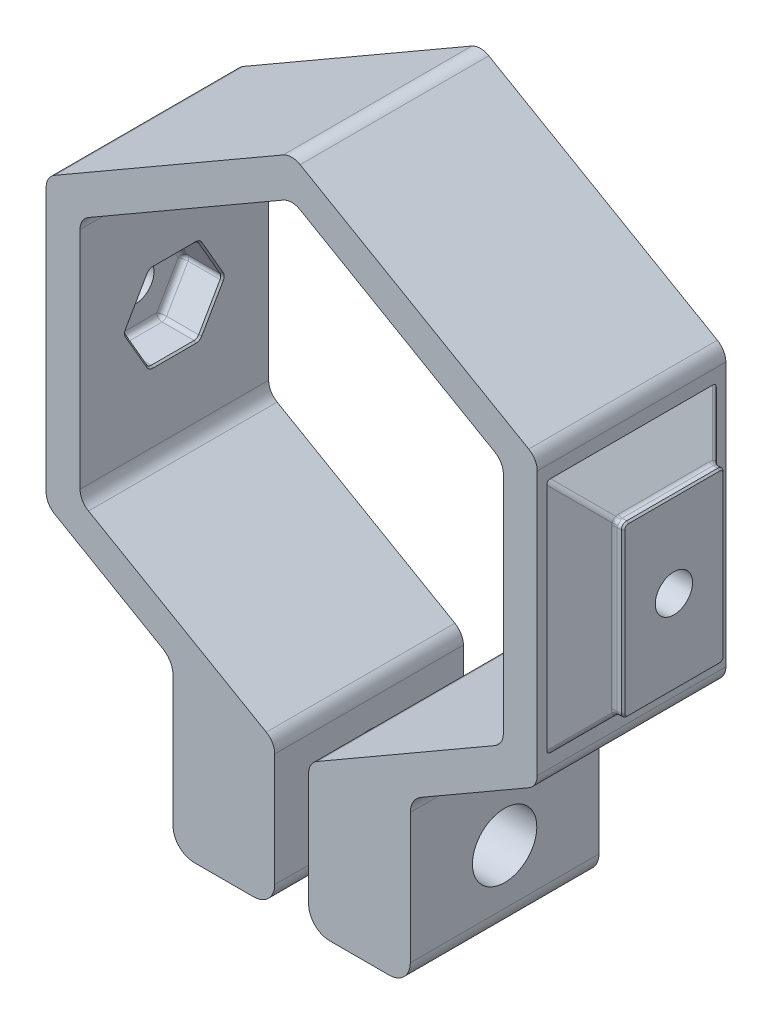
SolidWorks part; units mm, degrees
ref_plane "Front" through (0, 0, 0) normal (0, 0, 1) x (1, 0, 0)
ref_plane "Top" through (0, 0, 0) normal (0, 1, 0) x (1, 0, 0)
ref_plane "Right" through (0, 0, 0) normal (1, 0, 0) x (0, 0, -1)
sketch "Sketch1" plane through (0, 0, 0) normal (0, 0, 1) x (1, 0, 0)
  line L1 (0, 18.3169) -> (-15.8629, 9.1585)
  line L2 (-15.8629, 9.1585) -> (-15.8629, -9.1585)
  line L3 (-15.8629, -9.1585) -> (0, -18.3169)
  line L4 (0, -18.3169) -> (15.8629, -9.1585)
  line L5 (15.8629, -9.1585) -> (15.8629, 9.1585)
  line L6 (15.8629, 9.1585) -> (0, 18.3169)
  line L7 (0, 21.2499) -> (-18.4029, 10.6249)
  line L8 (-18.4029, 10.6249) -> (-18.4029, -10.6249)
  line L9 (-18.4029, -10.6249) -> (0, -21.2499)
  line L10 (0, -21.2499) -> (18.4029, -10.6249)
  line L11 (18.4029, -10.6249) -> (18.4029, 10.6249)
  line L12 (18.4029, 10.6249) -> (0, 21.2499)
  circle A0 centre (0, 0) radius 15.8629 construction
  circle A1 centre (0, 0) radius 18.4029 construction
  dimension "D1" = 36.8058
  dimension "D2" = 2.54
extrude "Boss-Extrude9" add sketch "Sketch1" along normal blind 14.1376 contours L10 L6 L5 L4 L3 L2 L1 region at (8.9204, 15.4505, 0)
sketch "Sketch17" plane through (-18.4029, 0, 0) normal (-1, 0, 0) x (0, 0, 1)
  line L0 (7.0688, 6.35) -> (7.0688, 10.6249) construction
  line L1 (3.2588, -6.35) -> (10.8788, -6.35)
  line L2 (3.2588, -6.35) -> (3.2588, 6.35)
  line L3 (3.2588, 6.35) -> (10.8788, 6.35)
  line L4 (10.8788, -6.35) -> (10.8788, 6.35)
  line L5 (3.2588, -6.35) -> (10.8788, 6.35) construction
  line L6 (3.2588, 6.35) -> (10.8788, -6.35) construction
  line L8 (7.0688, -6.35) -> (7.0688, -10.6249) construction
  line L11 (14.1376, 0) -> (10.8788, 0) construction
  line L14 (0, 0) -> (3.2588, 0) construction
  line L16 (14.1376, 10.6249) -> (14.1376, -10.6249) construction
  line L17 (14.1376, -10.6249) -> (0, -10.6249) construction
  line L18 (14.1376, 10.6249) -> (0, 10.6249) construction
  point P0 (7.0688, 0)
  dimension "D1" = 12.7
  dimension "D2" = 7.62
extrude "Boss-Extrude10" add sketch "Sketch17" along normal blind 3.175
chamfer "Chamfer1" distance 2.54 angle 45 4 edges at (-18.4029, -6.35, 7.0688) (-18.4029, 0, 3.2588) (-18.4029, 6.35, 7.0688) (-18.4029, 0, 10.8788)
sketch "Sketch18" plane through (18.4029, 0, 0) normal (1, 0, 0) x (0, 0, -1)
  line L1 (-7.0688, 6.35) -> (-7.0688, 10.6249) construction
  line L2 (-10.8788, -6.35) -> (-3.2588, -6.35)
  line L3 (-10.8788, -6.35) -> (-10.8788, 6.35)
  line L4 (-10.8788, 6.35) -> (-3.2588, 6.35)
  line L5 (-3.2588, -6.35) -> (-3.2588, 6.35)
  line L6 (-10.8788, -6.35) -> (-3.2588, 6.35) construction
  line L7 (-10.8788, 6.35) -> (-3.2588, -6.35) construction
  line L9 (-14.1376, 0) -> (-10.8788, 0) construction
  line L11 (-7.0688, -6.35) -> (-7.0688, -10.6249) construction
  line L13 (-3.2588, 0) -> (0, 0) construction
  line L18 (-14.1376, -10.6249) -> (-14.1376, 10.6249) construction
  line L19 (-14.1376, 10.6249) -> (0, 10.6249) construction
  point P0 (-7.0688, 0)
  dimension "D1" = 7.62
  dimension "D2" = 12.7
extrude "Boss-Extrude11" add sketch "Sketch18" along normal blind 3.175
chamfer "Chamfer2" distance 2.54 angle 45 4 edges at (18.4029, -6.35, 7.0688) (18.4029, 0, 10.8788) (18.4029, 6.35, 7.0688) (18.4029, 0, 3.2588)
sketch "Sketch19" plane through (21.5779, 0, 0) normal (1, 0, 0) x (0, 0, -1)
  line L3 (-10.8788, 6.35) -> (-3.2588, -6.35) construction
  line L4 (-10.8788, -6.35) -> (-3.2588, 6.35) construction
  circle A0 centre (-7.0688, 0) radius 1.397
  dimension "D1" = 2.794
extrude "Cut-Extrude12" cut sketch "Sketch19" against normal up to next
sketch "Sketch20" plane through (-21.5779, 0, 0) normal (-1, 0, 0) x (0, 0, 1)
  line L0 (3.2588, 6.35) -> (10.8788, -6.35) construction
  line L3 (10.8788, 6.35) -> (3.2588, -6.35) construction
  circle A0 centre (7.0688, 0) radius 1.397
  dimension "D1" = 2.794
extrude "Cut-Extrude13" cut sketch "Sketch20" against normal up to next
sketch "Sketch26" plane through (0, 0, 14.1376) normal (0, 0, 1) x (1, 0, 0)
  line L1 (1.27, -16.4697) -> (-1.27, -16.4697)
  line L2 (1.27, -16.4697) -> (1.27, -31.7097)
  line L3 (1.27, -31.7097) -> (-1.27, -31.7097)
  line L4 (-1.27, -16.4697) -> (-1.27, -31.7097)
  line L5 (1.27, -16.4697) -> (-1.27, -31.7097) construction
  line L6 (1.27, -31.7097) -> (-1.27, -16.4697) construction
  point P0 (0, -24.0897)
  dimension "D1" = 2.54
  dimension "D2" = 15.24
sketch "Sketch25" plane through (-15.8629, 0, 0) normal (1, 0, 0) x (0, 0, -1)
  line L1 (-5.2357, 3.175) -> (-8.9019, 3.175)
  line L2 (-8.9019, 3.175) -> (-10.735, 0)
  line L3 (-10.735, 0) -> (-8.9019, -3.175)
  line L4 (-8.9019, -3.175) -> (-5.2357, -3.175)
  line L5 (-5.2357, -3.175) -> (-3.4026, 0)
  line L6 (-3.4026, 0) -> (-5.2357, 3.175)
  circle A0 centre (-7.0688, 0) radius 3.175 construction
  circle A3 centre (-7.0688, 0) radius 1.397 construction
  dimension "D1" = 6.35
extrude "Cut-Extrude15" cut sketch "Sketch25" against normal blind 2.921
extrude "Cut-Extrude16" cut sketch "Sketch25<2>" along normal blind 2.921 from surface starting at face at (15.8629, -1.397, 7.0688)
sketch "Sketch25<2>" plane through (-15.8629, 0, 0) normal (1, 0, 0) x (0, 0, -1) same geometry as "Sketch25"
sketch "Sketch21" plane through (0, 0, 14.1376) normal (0, 0, 1) x (1, 0, 0)
  line L2 (0, -21.2499) -> (0, -28.386) construction
  line L3 (-8.89, -16.1172) -> (-8.89, -28.386)
  line L4 (-8.89, -28.386) -> (8.89, -28.386)
  line L5 (8.89, -16.1172) -> (8.89, -28.386)
  line L8 (0, -21.2499) -> (-8.89, -16.1172)
  line L9 (8.89, -16.1172) -> (0, -21.2499)
  line L10 (-18.4029, -10.6249) -> (0, -21.2499) construction
  line L11 (0, -21.2499) -> (18.4029, -10.6249) construction
  dimension "D1" = 17.78
  dimension "D2" = 12.2688
extrude "Boss-Extrude12" add sketch "Sketch21" against normal blind 14.1376
extrude "Cut-Extrude17" cut sketch "Sketch26" against normal through all both and the other way through all
sketch "Sketch27" plane through (8.89, 0, 0) normal (1, 0, 0) x (0, 0, -1)
  circle A0 centre (-7.0688, -22.7099) radius 2.413
  point P4 (-7.0688, -22.7099)
  dimension "D1" = 4.826
extrude "Cut-Extrude18" cut sketch "Sketch27" against normal through all both and the other way through all
fillet "Fillet1" radius 1.27 7 edges at (-15.8629, -9.1585, 7.0688) (-15.8629, 9.1585, 7.0688) (0, 18.3169, 7.0688) (15.8629, 9.1585, 7.0688) (15.8629, -9.1585, 7.0688) (1.27, -17.5837, 7.0688) (-1.27, -17.5837, 7.0688)
fillet "Fillet4" radius 1.27 5 edges at (18.4029, -10.6249, 7.0688) (-18.4029, -10.6249, 7.0688) (0, 21.2499, 7.0688) (18.4029, 10.6249, 7.0688) (-18.4029, 10.6249, 7.0688)
fillet "Fillet8" radius 1.5875 6 edges at (-8.89, -16.1172, 7.0688) (8.89, -16.1172, 7.0688) (8.89, -28.386, 7.0688) (1.27, -28.386, 7.0688) (-1.27, -28.386, 7.0688) (-8.89, -28.386, 7.0688)
fillet "Fillet9" radius 0.3969 32 edges at (21.2604, -6.35, 3.2588) (21.2604, -6.35, 10.8788) (21.2604, 6.35, 3.2588) (21.2604, 6.35, 10.8788) (-21.2604, -6.35, 10.8788) (-21.2604, -6.35, 3.2588) (-21.2604, 6.35, 3.2588) (-21.2604, 6.35, 10.8788) (-17.3234, -3.175, 5.2357) (-17.3234, -3.175, 8.9019) (-17.3234, 0, 10.735) (-17.3234, 3.175, 8.9019) (-17.3234, 3.175, 5.2357) (-17.3234, 0, 3.4026) (-18.7839, -3.175, 7.0688) (-18.7839, -1.5875, 9.8185) (-18.7839, 1.5875, 9.8185) (-18.7839, 3.175, 7.0688) (-18.7839, 1.5875, 4.3192) (-18.7839, -1.5875, 4.3192) (17.3234, 3.175, 5.2357) (17.3234, 3.175, 8.9019) (17.3234, 0, 10.735) (17.3234, -3.175, 8.9019) (17.3234, -3.175, 5.2357) (17.3234, 0, 3.4026) (18.7839, 3.175, 7.0688) (18.7839, 1.5875, 9.8185) (18.7839, -1.5875, 9.8185) (18.7839, -3.175, 7.0688) (18.7839, -1.5875, 4.3192) (18.7839, 1.5875, 4.3192)
fillet "Fillet10" radius 0.3969 32 edges at (20.9429, -6.35, 7.0688) (-20.9429, 0, 3.2588) (20.9731, -6.3198, 3.5038) (20.9731, -6.3198, 10.6338) (-20.9731, -6.105, 3.289) (-20.9731, 6.105, 3.289) (20.9731, -6.105, 3.289) (20.9731, -6.105, 10.8486) (-20.9731, -6.3198, 3.5038) (-20.9731, 6.3198, 3.5038) (20.9429, 0, 3.2588) (20.9429, 0, 10.8788) (-20.9429, -6.35, 7.0688) (-20.9429, 6.35, 7.0688) (20.9731, 6.105, 3.289) (20.9731, 6.105, 10.8486) (-20.9731, -6.3198, 10.6338) (-20.9731, 6.3198, 10.6338) (20.9731, 6.3198, 3.5038) (20.9731, 6.3198, 10.6338) (-20.9731, -6.105, 10.8486) (-20.9731, 6.105, 10.8486) (19.731, -7.5619, 2.0469) (19.731, -7.5619, 12.0907) (19.731, 7.5619, 2.0469) (20.9429, 6.35, 7.0688) (19.731, 7.5619, 12.0907) (-19.731, -7.5619, 12.0907) (-19.731, -7.5619, 2.0469) (-19.731, 7.5619, 2.0469) (-20.9429, 0, 10.8788) (-19.731, 7.5619, 12.0907)
chamfer "Chamfer4" distance 0.127 angle 45 40 edges at (21.5779, 0, 3.2588) (21.5779, 6.2338, 3.3751) (21.5779, -6.2338, 3.3751) (21.5779, 6.35, 7.0688) (21.5779, -6.35, 7.0688) (21.5779, 6.2338, 10.7626) (21.5779, -6.2338, 10.7626) (21.5779, 0, 10.8788) (-21.5779, 0, 3.2588) (-21.5779, -6.2338, 3.3751) (-21.5779, 6.2338, 3.3751) (-21.5779, -6.35, 7.0688) (-21.5779, 6.35, 7.0688) (-21.5779, -6.2338, 10.7626) (-21.5779, 6.2338, 10.7626) (-21.5779, 0, 10.8788) (15.8629, -1.5875, 9.8185) (15.8629, -3.1218, 8.8712) (15.8629, 0, 10.6736) (15.8629, -3.175, 7.0688) (15.8629, 1.5875, 9.8185) (15.8629, -3.1218, 5.2664) (15.8629, 3.1218, 8.8712) (15.8629, -1.5875, 4.3192) (15.8629, 3.175, 7.0688) (15.8629, 0, 3.464) (15.8629, 3.1218, 5.2664) (15.8629, 1.5875, 4.3192) (-15.8629, -1.5875, 9.8185) (-15.8629, -3.1218, 8.8712) (-15.8629, 0, 10.6736) (-15.8629, -3.175, 7.0688) (-15.8629, 1.5875, 9.8185) (-15.8629, -3.1218, 5.2664) (-15.8629, 3.1218, 8.8712) (-15.8629, -1.5875, 4.3192) (-15.8629, 3.175, 7.0688) (-15.8629, 0, 3.464) (-15.8629, 3.1218, 5.2664) (-15.8629, 1.5875, 4.3192)
